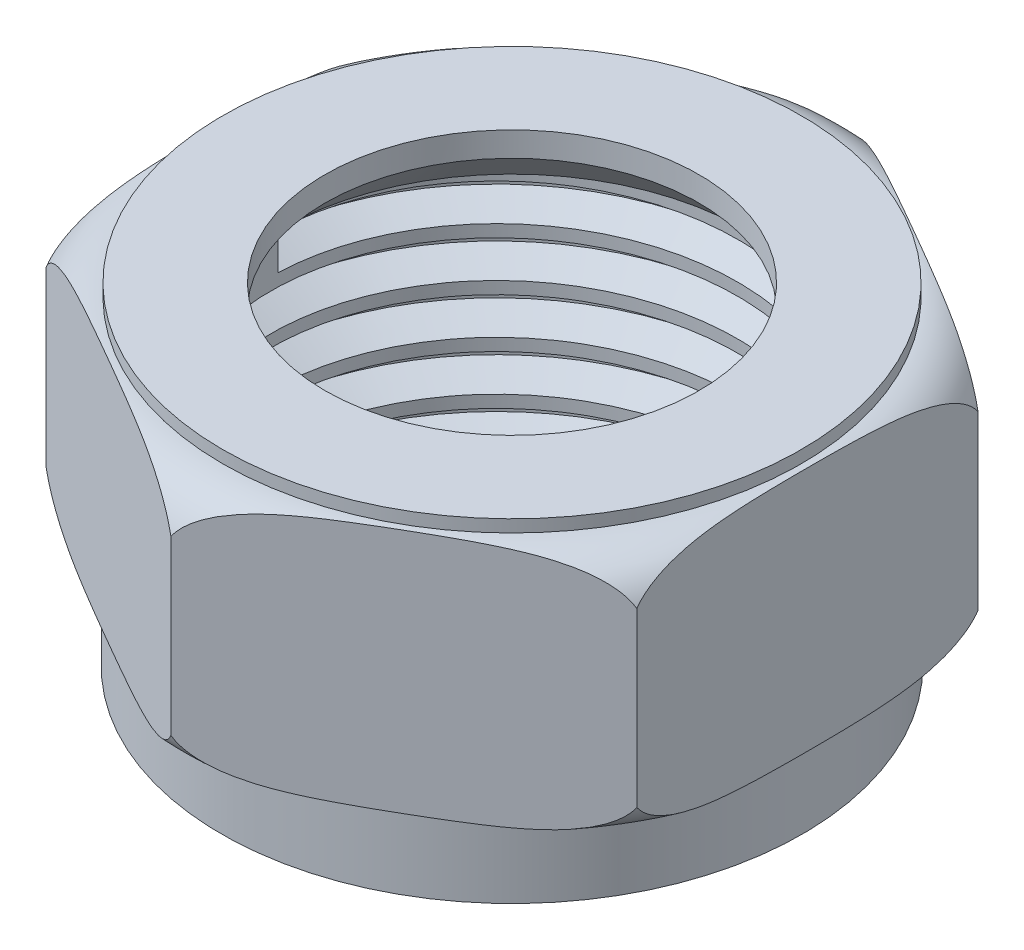
SolidWorks part; units mm, degrees
ref_plane "Front" through (0, 0, 0) normal (0, 0, 1) x (1, 0, 0)
ref_plane "Top" through (0, 0, 0) normal (0, 1, 0) x (1, 0, 0)
ref_plane "Right" through (0, 0, 0) normal (1, 0, 0) x (0, 0, -1)
ref_axis "Axis1" through (0, 55, 0) along (0, -1, 0)
ref_axis "Axis2" through (88.99, 0, 0) along (-1, 0, 0)
ref_axis "Axis3" through (0, 0, 55) along (0, 0, -1)
sketch "Sketch1" plane through (0, 0, 0) normal (0, 1, 0) x (1, 0, 0)
  line L1 (12, 6.9282) -> (0, 13.8564)
  line L2 (0, 13.8564) -> (-12, 6.9282)
  line L3 (-12, 6.9282) -> (-12, -6.9282)
  line L4 (-12, -6.9282) -> (0, -13.8564)
  line L5 (0, -13.8564) -> (12, -6.9282)
  line L6 (12, -6.9282) -> (12, 6.9282)
  circle A0 centre (0, 0) radius 12 construction
  dimension "D1" = 24
extrude "Boss-Extrude1" add sketch "Sketch1" along normal mid plane 13.5
sketch "Sketch2" plane through (0, 6.75, 0) normal (0, 1, 0) x (1, 0, 0)
  line L6 (12, -6.9282) -> (12, 6.9282)
  line L7 (12, 6.9282) -> (0, 13.8564)
  line L8 (0, 13.8564) -> (-12, 6.9282)
  line L9 (-12, 6.9282) -> (-12, -6.9282)
  line L10 (-12, -6.9282) -> (0, -13.8564)
  line L11 (0, -13.8564) -> (12, -6.9282)
  line L12 (12, -6.9282) -> (12, 6.9282)
  line L13 (12, 6.9282) -> (0, 13.8564)
  line L14 (0, 13.8564) -> (-12, 6.9282)
  line L15 (-12, 6.9282) -> (-12, -6.9282)
  line L16 (-12, -6.9282) -> (0, -13.8564)
  line L17 (0, -13.8564) -> (12, -6.9282)
  circle A0 centre (0, 0) radius 11.75
  dimension "D1" = 23.5
  dimension "D2" = 0
extrude "Cut-Extrude1" cut sketch "Sketch2" against normal blind 0.5
sketch "Sketch3" plane through (0, -6.75, 0) normal (0, -1, 0) x (1, 0, 0)
  line L6 (12, -6.9282) -> (12, 6.9282)
  line L7 (12, 6.9282) -> (0, 13.8564)
  line L8 (0, 13.8564) -> (-12, 6.9282)
  line L9 (-12, 6.9282) -> (-12, -6.9282)
  line L10 (-12, -6.9282) -> (0, -13.8564)
  line L11 (0, -13.8564) -> (12, -6.9282)
  line L12 (12, -6.9282) -> (12, 6.9282)
  line L13 (12, 6.9282) -> (0, 13.8564)
  line L14 (0, 13.8564) -> (-12, 6.9282)
  line L15 (-12, 6.9282) -> (-12, -6.9282)
  line L16 (-12, -6.9282) -> (0, -13.8564)
  line L17 (0, -13.8564) -> (12, -6.9282)
  circle A0 centre (0, 0) radius 11.8
  dimension "D1" = 23.6
  dimension "D2" = 0
extrude "Cut-Extrude2" cut sketch "Sketch3" against normal blind 3
ref_plane "Plane2" through (0, 1.25, 0) normal (0, 1, 0) x (1, 0, 0)
sketch "Sketch8" plane through (0, 0, 0) normal (1, 0, 0) x (0, 0, -1)
  line L0 (0, 6.75) -> (0, -6.75) construction
  line L1 (11.75, 6.75) -> (-11.75, 6.75) construction
  line L2 (-11.8, -6.75) -> (11.8, -6.75) construction
  line L3 (-13.8564, 6.25) -> (-13.8564, -3.75) construction
  line L4 (-13.8564, 6.25) -> (-6.9282, 6.25) construction
  line L5 (-11.75, 6.25) -> (-13.8564, 6.25)
  line L6 (-13.8564, 6.25) -> (-13.8564, 4.75)
  arc A0 (-11.75, 6.25) -> (-13.8564, 4.75) centre (-11.75, 4.021) ccw
  point P14 (0, 0)
  point P17 (-13.8564, 5.1084)
  dimension "D1" = 1.5
revolve "Cut-Revolve2" cut sketch "Sketch8" angle 360 about L0
mirror "Mirror1" about plane through (0, 1.25, 0) normal (0, 1, 0) of "Cut-Revolve2"
sketch "Sketch5" plane through (0, 0, 0) normal (1, 0, 0) x (0, 0, -1)
  line L0 (0, 6.75) -> (0, -6.75) construction
  line L1 (11.75, 6.75) -> (-11.75, 6.75) construction
  line L2 (-11.8, -6.75) -> (11.8, -6.75) construction
  line L3 (-7.6, 6.75) -> (-7.6, 5.75)
  line L4 (-7.6, 5.75) -> (-9.5, 3.85)
  line L5 (-9.5, 3.85) -> (-9.5, -6.75)
  line L6 (-9.5, -6.75) -> (0, -6.75)
  line L7 (-7.6, 6.75) -> (0, 6.75)
  line L10 (0, 6.75) -> (0, -6.75)
  point P8 (-8.7505, 6.1348)
  point P11 (-7.6, 6.4474)
  point P12 (-9.5, 4.5442)
  dimension "D1" = 19
  dimension "D2" = 1
  dimension "D3" = 45
  dimension "D4" = 15.2
revolve "Cut-Revolve1" cut sketch "Sketch5" angle 360 about L0
thread "Thread1" pitch 2 method cut profile "Thread Profile1" start angle 0, offset 0, length 20, pitch 2, diameter 19
ref_plane "Plane1" through (-9.5, 3.85, 0) normal (0, 0, 1) x (-1, 0, 0)
sketch "Thread Profile1" plane through (-9.5, 3.85, 0) normal (0, 0, 1) x (-1, 0, 0)
  line L0 (0, 0) -> (0, 2) construction
  line L1 (0, 0) -> (1.0825, 0.625)
  line L2 (1.0825, 0.625) -> (1.0825, 0.875)
  line L3 (1.0825, 0.875) -> (0, 1.5)
  line L4 (1.0825, 0.75) -> (0, 0.75) construction
  line L11 (0, 0) -> (0, 1.5)
  point P2 (0, 0)
  dimension "Pitch" = 2
  dimension "Profile_Angle" = 60
  dimension "Profile_Land" = 0.25
  dimension "Profile_Height" = 1.0825
